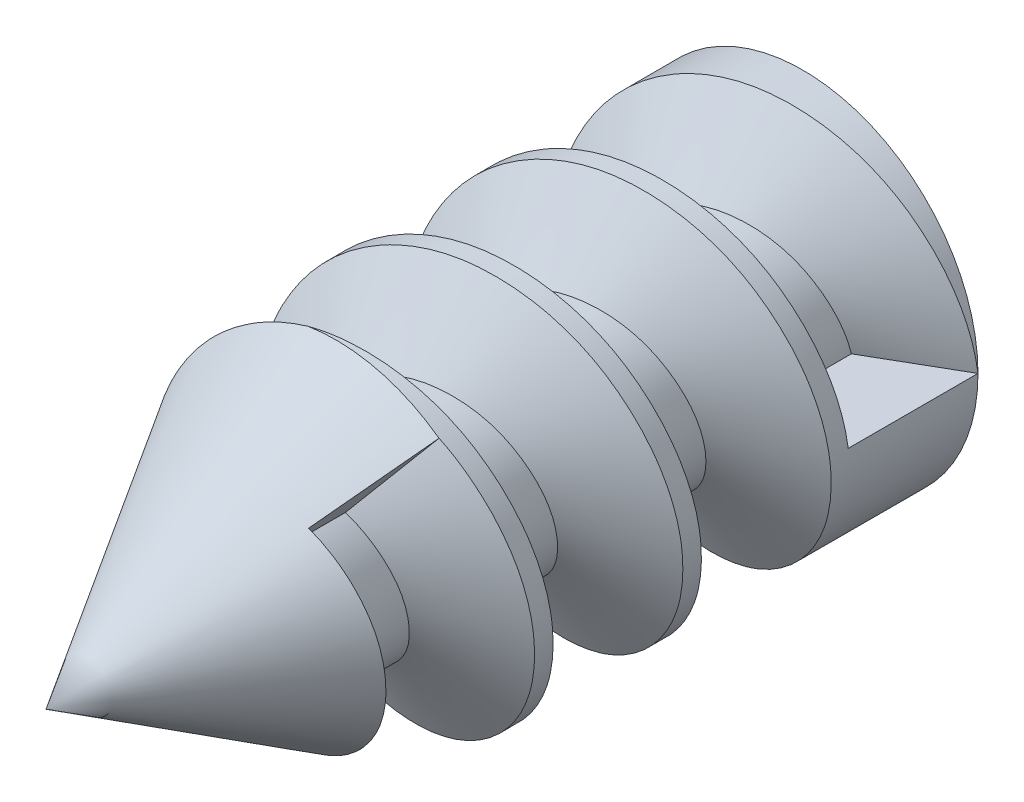
SolidWorks part; units mm, degrees
ref_plane "前视基准面" through (0, 0, 0) normal (0, 0, 1) x (1, 0, 0)
ref_plane "上视基准面" through (0, 0, 0) normal (0, 1, 0) x (1, 0, 0)
ref_plane "右视基准面" through (0, 0, 0) normal (1, 0, 0) x (0, 0, -1)
sketch "草图1" plane through (0, 0, 0) normal (0, 0, 1) x (1, 0, 0)
  circle A0 centre (0, 0) radius 1.5
extrude "凸台-拉伸1" add sketch "草图1" along normal blind 4 contours A0
sketch "草图2" plane through (0, 0, 0) normal (1, 0, 0) x (0, 0, -1)
  line L0 (-4, 0) -> (-6.481, 0)
  line L1 (-4, 1.5) -> (-4, -1.5) construction
  line L2 (-6.481, 0) -> (-4, -1.5)
  line L3 (-4, -1.5) -> (-4, 0)
  point P5 (-6.481, 0)
revolve "旋转1" add sketch "草图2" angle 360 about L0
thread "螺纹线1" pitch 1.27 method cut profile "螺纹线轮廓1" start angle 0, offset 0, length 0, pitch 1.27, diameter 3
ref_plane "基准面1" through (1.5, 0, 0) normal (0, -1, 0) x (1, 0, 0)
sketch "螺纹线轮廓1" plane through (1.5, 0, 0) normal (0, -1, 0) x (1, 0, 0)
  line L0 (0, 0) -> (0, 1.27) construction
  line L11 (0, 0) -> (0, 1.1112)
  line L12 (0, 1.1112) -> (-0.6874, 0.7144)
  line L13 (-0.6874, 0.7144) -> (-0.6874, 0.3969)
  line L15 (-0.6874, 0.3969) -> (0, 0)
  line L17 (-0.6874, 0.5556) -> (0, 0.5556) construction
  point P2 (0, 0)
  dimension "Pitch" = 1.27
  dimension "Profile_Angle" = 60
  dimension "Profile_Land" = 0.3175
  dimension "Profile_Height" = 0.6874
